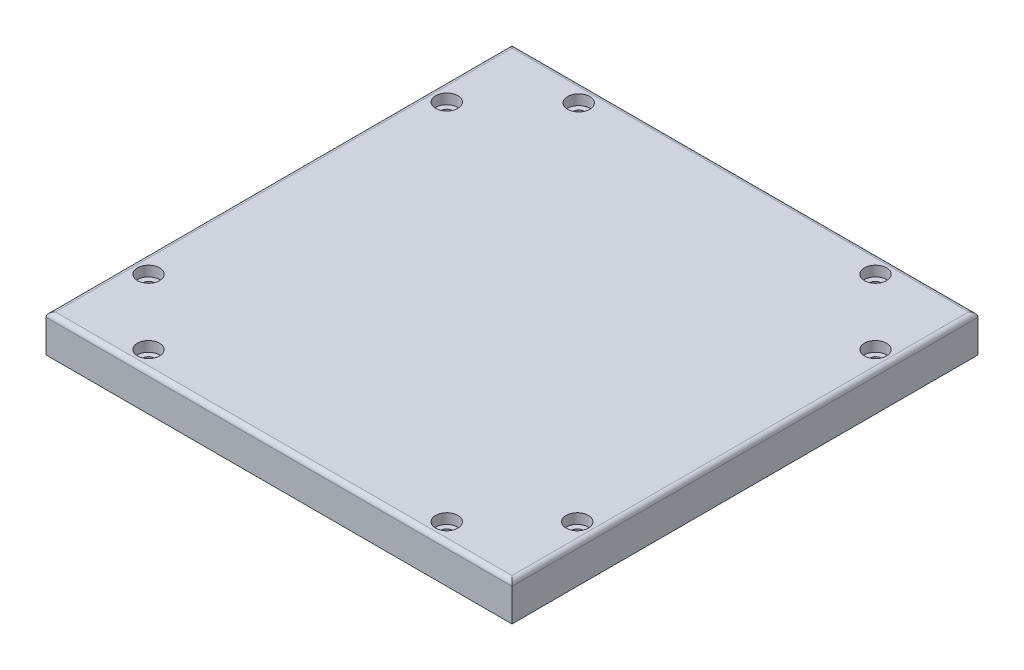
SolidWorks part; units mm, degrees
ref_plane "Front Plane" through (0, 0, 0) normal (0, 0, 1) x (1, 0, 0)
ref_plane "Top Plane" through (0, 0, 0) normal (0, 1, 0) x (1, 0, 0)
ref_plane "Right Plane" through (0, 0, 0) normal (1, 0, 0) x (0, 0, -1)
sketch "Sketch3" plane through (0, 0, 0) normal (0, 1, 0) x (1, 0, 0)
  line L1 (-50, 50) -> (50, 50)
  line L2 (-50, 50) -> (-50, -50)
  line L3 (-50, -50) -> (50, -50)
  line L4 (50, 50) -> (50, -50)
  line L5 (-50, 50) -> (50, -50) construction
  line L6 (-50, -50) -> (50, 50) construction
  point P0 (0, 0)
extrude "Boss-Extrude2" add sketch "Sketch3" along normal blind 8
sketch "Sketch4" plane through (0, 8, 0) normal (0, 1, 0) x (1, 0, 0)
  line L0 (50, -50) -> (-50, 50) construction
  line L1 (-50, 50) -> (50, 50) construction
  line L2 (50, 50) -> (-50, -50) construction
  line L3 (-50, -50) -> (50, -50) construction
  line L4 (-50, -50) -> (-42, -50) construction
  line L5 (-42, -50) -> (-42, 50) construction
  line L6 (50, -50) -> (42, -50) construction
  line L7 (42, -50) -> (42, 50) construction
  line L8 (42, 50) -> (50, 50) construction
  line L9 (50, 50) -> (50, 42) construction
  line L10 (50, 42) -> (-50, 42) construction
  line L11 (50, -50) -> (50, -42) construction
  line L12 (50, -42) -> (-50, -42) construction
  line L13 (-50, 50) -> (-50, -50) construction
  line L14 (50, -46) -> (32, -46) construction
  line L15 (-50, -46) -> (-32, -46) construction
  line L16 (42, -50) -> (50, -50) construction
  line L17 (50, -50) -> (46, -50) construction
  line L18 (46, -50) -> (46, -32) construction
  line L19 (50, 46) -> (32, 46) construction
  line L20 (50, 50) -> (42, 50) construction
  line L21 (42, 50) -> (46, 50) construction
  line L22 (46, 50) -> (46, 32) construction
  line L23 (-50, 50) -> (-42, 50) construction
  line L24 (-42, 50) -> (-46, 50) construction
  line L25 (-46, 50) -> (-46, 32) construction
  line L26 (-50, 42) -> (-50, 50) construction
  line L27 (-50, 50) -> (-50, 46) construction
  line L28 (-42, -50) -> (-50, -50) construction
  line L29 (-50, -50) -> (-46, -50) construction
  line L30 (-46, -50) -> (-46, -32) construction
  line L31 (-49.6798, 46) -> (-31.6798, 46) construction
hole_wizard "CBORE for #2 Socket Head Cap Screw1" positions "3DSketch1" profile "Sketch5" counterbore size "#2" standard "ANSI Inch" end condition through all
sketch3d "3DSketch1"
  line L0 (50, 8, 46) -> (32, 8, 46) construction
  point P0 (-46, 8, 32)
  point P3 (-32, 8, 46)
  point P6 (-46, 8, -32)
  point P9 (-31.6798, 8, -46)
  point P12 (32, 8, -46)
  point P15 (46, 8, -32)
  point P18 (32, 8, 46)
  point P22 (46, 8, 32)
sketch "Sketch5" plane through (-46, 8, 32) normal (1, 0, 0) x (0, 0, 1)
  line L0 (0, 0) -> (0, 8)
  line L1 (0, 8) -> (1.2192, 8)
  line L3 (1.2192, 8) -> (1.2192, 2.1844)
  line L4 (1.2192, 2.1844) -> (2.3812, 2.1844)
  line L5 (2.3812, 2.1844) -> (2.3812, 0)
  line L7 (2.3812, 0) -> (0, 0)
  line L11 (0, -6.35) -> (0, 107.95) construction
  dimension "Thru Hole Dia." = 2.4384
  dimension "Thru Hole Depth" = 8
  dimension "C'Bore Dia." = 4.7625
  dimension "C'Bore Depth" = 2.1844
fillet "Fillet1" radius 1 4 edges at (0, 8, 50) (-50, 8, 0) (0, 8, -50) (50, 8, 0)
